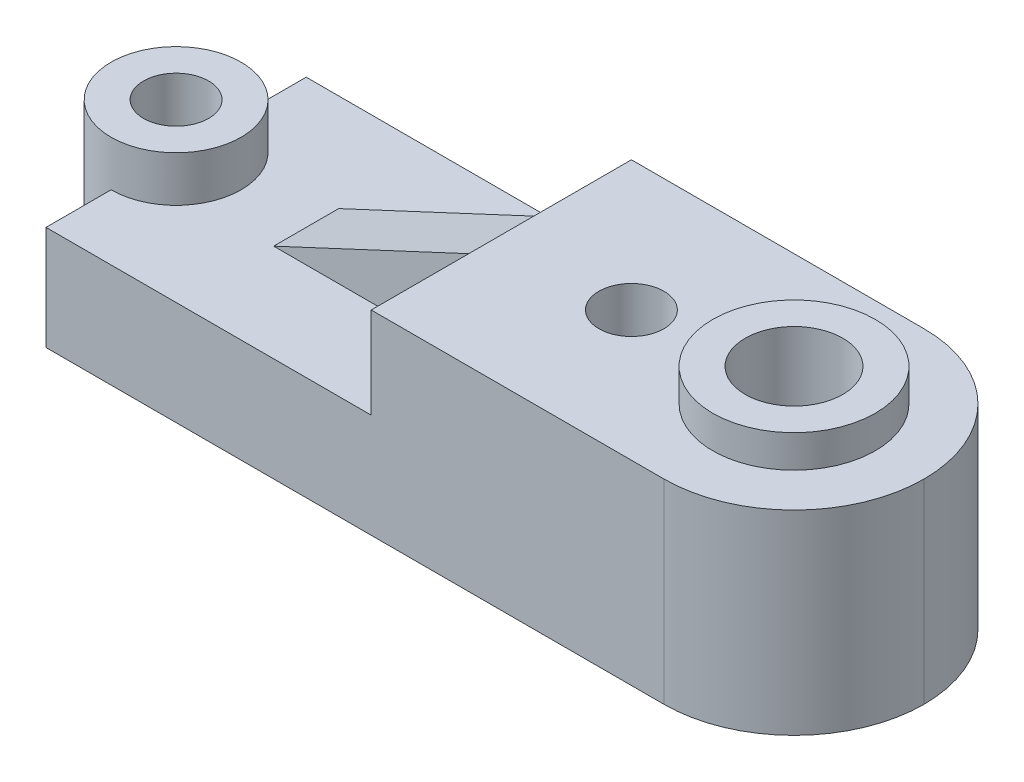
SolidWorks part; units mm, degrees
ref_plane "Front Plane" through (0, 0, 0) normal (0, 0, 1) x (1, 0, 0)
ref_plane "Top Plane" through (0, 0, 0) normal (0, 1, 0) x (1, 0, 0)
ref_plane "Right Plane" through (0, 0, 0) normal (1, 0, 0) x (0, 0, -1)
sketch "Sketch1" plane through (0, 0, 0) normal (0, 1, 0) x (1, 0, 0)
  line L1 (-57.5, 20) -> (57.5, 20)
  line L2 (-57.5, 20) -> (-57.5, -20)
  line L3 (-57.5, -20) -> (57.5, -20)
  line L4 (57.5, 20) -> (57.5, -20)
  line L5 (-57.5, 20) -> (57.5, -20) construction
  line L6 (-57.5, -20) -> (57.5, 20) construction
  point P0 (0, 0)
  dimension "D1" = 40
  dimension "D2" = 115
extrude "Boss-Extrude1" add sketch "Sketch1" along normal blind 16
sketch "Sketch2" plane through (0, 0, 0) normal (0, 1, 0) x (1, 0, 0)
  line L0 (-57.5, 20) -> (-57.5, -20) construction
  circle A0 centre (-57.5, 0) radius 10
  circle A1 centre (-57.5, 0) radius 5
  dimension "D1" = 20
  dimension "D2" = 10
extrude "Boss-Extrude2" add sketch "Sketch2" along normal blind 23
sketch "Sketch3" plane through (0, 0, 0) normal (0, 1, 0) x (1, 0, 0)
  line L0 (-57.5, 5) -> (-57.5, -5) construction
  circle A0 centre (-57.5, 0) radius 7.5
  dimension "D1" = 15
extrude "Cut-Extrude1" cut sketch "Sketch3" along normal blind 10
sketch "Sketch4" plane through (0, 0, 0) normal (0, 1, 0) x (1, 0, 0)
  circle A0 centre (-57.5, 0) radius 5 construction
  circle A1 centre (-57.5, 0) radius 5
extrude "Cut-Extrude2" cut sketch "Sketch4" along normal blind 36 and the other way blind 24
sketch "Sketch5" plane through (0, 16, 0) normal (0, 1, 0) x (1, 0, 0)
  line L0 (-57.5, -20) -> (57.5, -20) construction
  line L1 (57.5, 20) -> (-7.5, 20)
  line L2 (57.5, 20) -> (57.5, -20)
  line L3 (57.5, -20) -> (-7.5, -20)
  line L4 (-7.5, 20) -> (-7.5, -20)
  line L5 (-57.5, 20) -> (-57.5, 10) construction
  dimension "D1" = 50
extrude "Boss-Extrude3" add sketch "Sketch5" along normal blind 14
sketch "Sketch8" plane through (0, 0, 0) normal (0, 0, 1) x (1, 0, 0)
  line L0 (-37.5, 16) -> (-7.5, 30)
  line L1 (-7.5, 30) -> (-7.5, 16) construction
  dimension "D1" = 30
rib "Rib2" sketch "Sketch8" sketch "Sketch8" thickness 10 extrusion direction parallel to sketch draft on no parameters "D1"=10
fillet "Fillet3" radius 20 2 edges at (57.5, 15, -20) (57.5, 15, 20)
sketch "Sketch10" plane through (0, 30, 0) normal (0, 1, 0) x (1, 0, 0)
  circle A0 centre (37.5, 0) radius 12.5
  circle A1 centre (37.5, 0) radius 7.5
  dimension "D1" = 25
  dimension "D2" = 15
extrude "Boss-Extrude4" add sketch "Sketch10" along normal blind 5
sketch "Sketch11" plane through (0, 30, 0) normal (0, 1, 0) x (1, 0, 0)
  circle A0 centre (37.5, 0) radius 7.5 construction
  circle A1 centre (37.5, 0) radius 7.5
extrude "Cut-Extrude3" cut sketch "Sketch11" against normal through all
sketch "Sketch12" plane through (0, 30, 0) normal (0, 1, 0) x (1, 0, 0)
  circle A0 centre (12.5, 0) radius 5
  circle A1 centre (37.5, 0) radius 7.5 construction
  dimension "D2" = 10
  dimension "D1" = 25
extrude "Cut-Extrude4" cut sketch "Sketch12" against normal through all
sketch "Sketch13" plane through (0, 0, 0) normal (0, 1, 0) x (1, 0, 0)
  line L0 (37.5, -15) -> (-1.5, -15)
  line L1 (-1.5, -15) -> (-1.5, 15)
  line L2 (-1.5, 15) -> (37.5, 15)
  arc A0 (37.5, -15) -> (37.5, 15) centre (37.5, 0) ccw
  circle A1 centre (12.5, 0) radius 5 construction
  dimension "D1" = 30
  dimension "D2" = 14
extrude "Cut-Extrude5" cut sketch "Sketch13" along normal blind 20
sketch "Sketch14" plane through (0, 0, 0) normal (0, 1, 0) x (1, 0, 0)
  line L0 (-22.5, 10) -> (-1.5, 10)
  line L1 (-1.5, 15) -> (-1.5, -15) construction
  line L2 (-1.5, 10) -> (-1.5, -10)
  line L3 (-1.5, -10) -> (-22.5, -10)
  line L4 (-7.5, 20) -> (-7.5, 5) construction
  arc A0 (-22.5, 10) -> (-22.5, -10) centre (-22.5, 0) ccw
  dimension "D1" = 20
  dimension "D2" = 15
extrude "Cut-Extrude6" cut sketch "Sketch14" along normal blind 8
